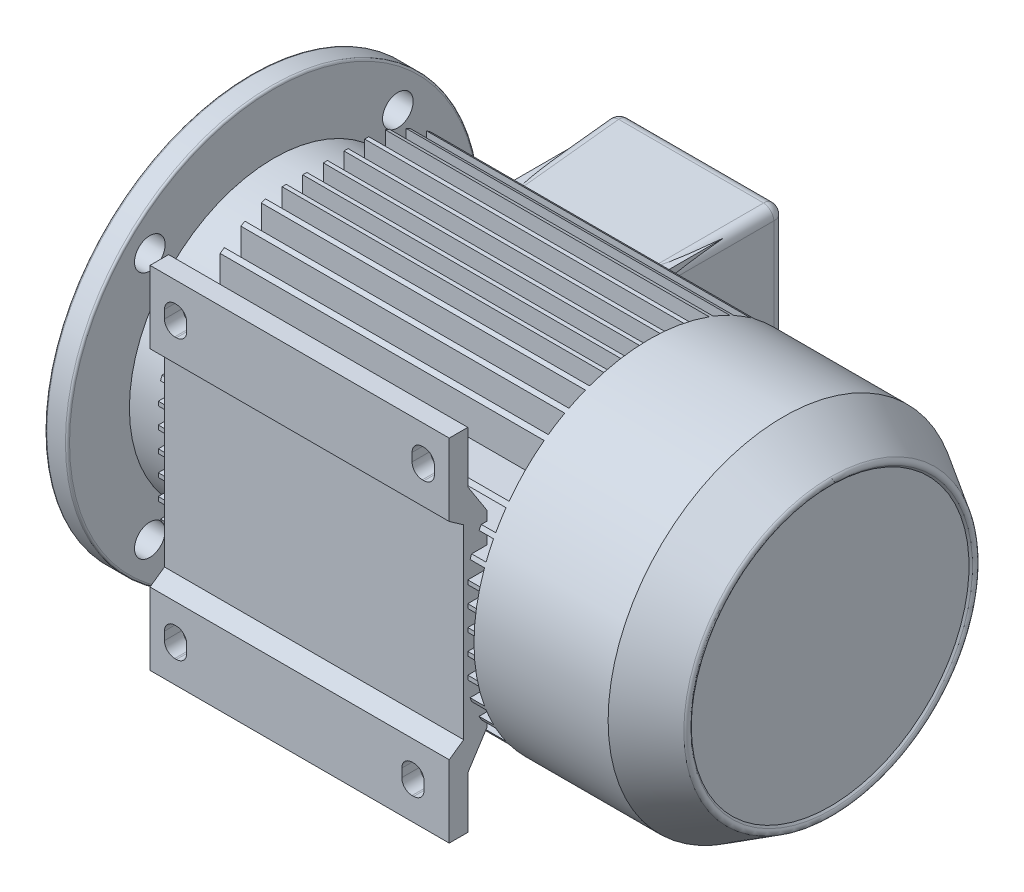
SolidWorks part; units mm, degrees
ref_plane "Front Plane" through (0, 0, 0) normal (0, 0, 1) x (1, 0, 0)
ref_plane "Top Plane" through (0, 0, 0) normal (0, 1, 0) x (1, 0, 0)
ref_plane "Right Plane" through (0, 0, 0) normal (1, 0, 0) x (0, 0, -1)
sketch "Sketch1" plane through (0, 0, 0) normal (0, 0, 1) x (1, 0, 0)
  line L0 (-2.3963, 0) -> (-25, 0)
  line L1 (-2.069, 71.2414) -> (-25, 85)
  line L2 (-2.3963, 0) -> (-2.3963, 67.3059)
  line L3 (-90, 85) -> (-90, 84)
  line L4 (-25, 85) -> (-90, 85)
  line L5 (-90, 85) -> (-90, 84)
  line L6 (-87, 0) -> (-25, 0)
  line L7 (-2.3963, 67.3059) -> (-1.6036, 68.1972)
  line L8 (-90, 84) -> (-87, 84)
  line L9 (-87, 84) -> (-87, 0)
  arc A0 (-1.6036, 68.1972) -> (-2.069, 71.2414) centre (-3.098, 69.5264) ccw
  dimension "D6" = 2
  dimension "D1" = 1
  dimension "D2" = 3
  dimension "D3" = 85
  dimension "D4" = 65
revolve "Revolve1" add sketch "Sketch1" angle 360 about L6
sketch "Sketch2" plane through (-87, 0, 0) normal (-1, 0, 0) x (0, 0, 1)
  circle A0 centre (0, 0) radius 70
extrude "Boss-Extrude2" add sketch "Sketch2" along normal blind 185
sketch "Sketch3" plane through (-87, 0, 0) normal (-1, 0, 0) x (0, 0, 1)
  line L0 (0, 0) -> (81, 0)
  line L1 (0, 0) -> (-81, 0)
  dimension "D1" = 81
  dimension "D2" = 81
extrude "Extrude-Thin1" add sketch "Sketch3" along normal blind 160 thin thin type mid plane wall 2
pattern_linear "LPattern3" count 6 spacing 10 along (0, -1, 0) count 6 spacing 10 along (0, 1, 0) of "Extrude-Thin1"
pattern_circular "CirPattern1" count 2 every 90 about axis through (0, 0, 0) along (1, 0, 0) of "LPattern3", "Extrude-Thin1"
sketch "Sketch5" plane through (-2.3963, 0, 0) normal (1, 0, 0) x (0, 0, -1)
  circle A0 centre (0, 0) radius 85
  circle A1 centre (0, 0) radius 122.685
extrude "Cut-Extrude1" cut sketch "Sketch5" against normal blind 411
sketch "Sketch6" plane through (0, 0, 0) normal (0, 1, 0) x (1, 0, 0)
  line L0 (-272, 0) -> (-237, 0)
  line L1 (-272, 70) -> (-272, -70) construction
  line L2 (-237, 0) -> (-237, 70)
  line L3 (-247, 70) -> (-272, 70) construction
  dimension "D1" = 35
ref_plane "Plane1" through (-237, 0, -70) normal (0, 0, -1) x (-1, 0, 0)
sketch "Sketch7" plane through (-237, 0, -70) normal (0, 0, -1) x (-1, 0, 0)
  line L0 (0, 37.5) -> (0, -37.5)
  line L1 (0, 37.5) -> (-75, 37.5)
  line L2 (-75, 37.5) -> (-75, -37.5)
  line L3 (-75, -37.5) -> (0, -37.5)
  line L4 (35, 0) -> (0, 0) construction
  dimension "D1" = 75
  dimension "D2" = 37.5
  dimension "D3" = 75
extrude "Boss-Extrude3" add sketch "Sketch7" along normal blind 10
sketch "Sketch8" plane through (0, 0, -80) normal (0, 0, -1) x (-1, 0, 0)
  line L1 (162, -37.5) -> (237, -37.5)
  line L2 (162, -37.5) -> (162, 37.5)
  line L3 (162, 37.5) -> (237, 37.5)
  line L4 (237, -37.5) -> (237, 37.5)
extrude "Boss-Extrude4" add sketch "Sketch8" along normal blind 55 draft 3 draft outward yes
sketch "Sketch9" plane through (0, 0, 0) normal (0, 1, 0) x (1, 0, 0)
  line L0 (-182.1286, 80) -> (-182.1286, 100)
  line L1 (-162, 80) -> (-237, 80) construction
  circle A0 centre (-217.1286, 112) radius 12
  circle A1 centre (-182.1286, 112) radius 12
  circle A2 centre (-182.1286, 112) radius 7.5
  circle A3 centre (-217.1286, 112) radius 7.5
  dimension "D2" = 24
  dimension "D4" = 35
  dimension "D5" = 15
  dimension "D6" = 15
  dimension "D1" = 20
  dimension "D3" = 32
extrude "Boss-Extrude5" add sketch "Sketch9" against normal blind 55 contours A0 A3 | A1 A2
fillet "Fillet1" radius 10 2 edges at (-182.1286, -55, -100) (-217.1286, -55, -100)
fillet "Fillet2" radius 5 4 edges at (-199.5, 40.3824, -135) (-239.8824, 0, -135) (-199.5, -40.3824, -135) (-159.1176, 0, -135)
fillet "Fillet3" radius 5 8 edges at (-160.7596, 38.7404, -133.4418) (-160.7596, -38.7404, -133.4418) (-238.2404, -38.7404, -133.4418) (-238.2404, 38.7404, -133.4418) (-160.6967, 38.8033, -104.8692) (-160.6967, -38.8033, -104.8692) (-238.3033, -38.8033, -104.8692) (-238.3033, 38.8033, -104.8692)
sketch "Sketch10" plane through (-272, 0, 0) normal (-1, 0, 0) x (0, 0, 1)
  circle A0 centre (0, 0) radius 70
  circle A1 centre (0, 0) radius 100
  dimension "D1" = 30
extrude "Boss-Extrude6" add sketch "Sketch10" along normal blind 11 separate body
sketch "Sketch11" plane through (-272, 0, 0) normal (-1, 0, 0) x (0, 0, 1)
  circle A0 centre (0, 0) radius 12
  dimension "D1" = 24
sketch "Sketch12" plane through (-283, 0, 0) normal (-1, 0, 0) x (0, 0, 1)
  line L0 (-60.1041, 60.1041) -> (0, 0)
  line L1 (0, 0) -> (-70, 0) construction
  circle A0 centre (-60.1041, 60.1041) radius 7.4187
  circle A1 centre (60.1041, 60.1041) radius 7.4187
  circle A2 centre (60.1041, -60.1041) radius 7.4187
  circle A3 centre (-60.1041, -60.1041) radius 7.4187
  dimension "D1" = 45
  dimension "D2" = 85
  dimension "D3" = 4
extrude "Cut-Extrude2" cut sketch "Sketch12" against normal blind 15 contours A1 | A2 | A3 | A0
sketch "Sketch13" plane through (0, 0, 0) normal (0, 1, 0) x (1, 0, 0)
  line L0 (-272, -100) -> (-242, -100)
  line L1 (-242, -100) -> (-97, -100)
  dimension "D1" = 30
  dimension "D2" = 145
ref_plane "Plane2" through (-242, 0, 100) normal (1, 0, 0) x (0, 0, -1)
sketch "Sketch14" plane through (-242, 0, 100) normal (1, 0, 0) x (0, 0, -1)
  line L0 (0, 0) -> (0, 50)
  line L1 (0, 50) -> (0, -50)
  line L2 (0, 50) -> (10, 50)
  line L3 (10, 50) -> (10, -50)
  line L4 (10, 50) -> (10, 85)
  line L5 (10, 85) -> (19, 85)
  line L6 (19, 85) -> (19, 60)
  line L7 (19, 60) -> (28.265, 45.597)
  line L8 (28.265, -45.597) -> (28.265, 45.597)
  line L9 (19, -60) -> (28.265, -45.597)
  line L10 (10, -50) -> (10, -85)
  line L11 (10, -85) -> (19, -85)
  line L12 (19, -85) -> (19, -60)
  circle A0 centre (100, 0) radius 85 construction
  dimension "D1" = 100
  dimension "D2" = 50
  dimension "D3" = 10
  dimension "D4" = 35
  dimension "D5" = 25
  dimension "D6" = 9
extrude "Boss-Extrude8" add sketch "Sketch14" along normal up to vertex (145 mm away) contours L11 L12 L9 L8 L7 L6 L5 L4 L3 L10 up to point (-97, 0, 100)
sketch "Sketch15" plane through (0, 0, 90) normal (0, 0, 1) x (1, 0, 0)
  line L0 (-242, 85) -> (-242, 50)
  line L1 (-242, -79.75) -> (-242, 79.75) construction
  line L2 (-242, 50) -> (-97, 50)
  line L3 (-97, -85) -> (-97, 85) construction
  line L4 (-97, 50) -> (-97, -50)
  line L5 (-97, -50) -> (-242, -50)
  line L6 (-242, -50) -> (-242, 50)
  line L7 (-252.2039, 50) -> (-92.0219, 50)
  line L8 (-92.0219, 50) -> (-92.0219, -50)
  line L9 (-92.0219, -50) -> (-252.2039, -50)
  line L10 (-252.2039, -50) -> (-252.2039, 50)
  line M1 (-242, 85) -> (-242, -85)
  line M3 (-97, -85) -> (-97, 85)
  dimension "D1" = 35
  dimension "D2" = 35
extrude "Cut-Extrude4" cut sketch "Sketch15" against normal blind 7 draft 35 contours L5 L2 M3 M1 | L9 L8 L7 M3 | L10 L9 L7 M1
sketch "Sketch16" plane through (0, 0, 90) normal (0, 0, 1) x (1, 0, 0)
  line L0 (-242, 75) -> (-235, 75)
  line L1 (-242, -79.75) -> (-242, 79.75) construction
  line L2 (-235, 75) -> (-235, 85)
  line L3 (-97, 85) -> (-242, 85) construction
  line L4 (-235, 70) -> (-235, 66)
  line L5 (-230, 75) -> (-229.2085, 75)
  line L6 (-224.2085, 70) -> (-224.2085, 66)
  line L7 (-229.2085, 61) -> (-230, 61)
  line L8 (-235, 75) -> (-224.2085, 75)
  arc A0 (-229.2085, 61) -> (-224.2085, 66) centre (-229.2085, 66) ccw
  arc A1 (-230, 61) -> (-235, 66) centre (-230, 66) cw
  arc A2 (-235, 70) -> (-230, 75) centre (-230, 70) cw
  arc A3 (-224.2085, 70) -> (-229.2085, 75) centre (-229.2085, 70) ccw
  point P14 (-235, 61)
  dimension "D4" = 5
  dimension "D1" = 7
  dimension "D2" = 10
  dimension "D3" = 14
extrude "Cut-Extrude6" cut sketch "Sketch16" against normal blind 27 contours L6 A3 L5 A2 L4 A1 L7 A0
pattern_linear "LPattern4" count 2 spacing 120 along (1, 0, 0) of "Cut-Extrude6"
pattern_linear "LPattern8" count 2 spacing 135 along (0, -1, 0) of "Cut-Extrude6"
pattern_linear "LPattern9" count 2 spacing 115 along (1, 0, 0) of "LPattern8"
fillet "Fillet4" radius 1 3 edges at (-272, 0, 100) (-283, 0, 100) (-283, 0, 70)
sketch "Sketch17" plane through (-272, 0, 0) normal (-1, 0, 0) x (0, 0, 1)
  circle A0 centre (0, 0) radius 30
  dimension "D1" = 60
extrude "Cut-Extrude7" cut sketch "Sketch17" against normal blind 60
